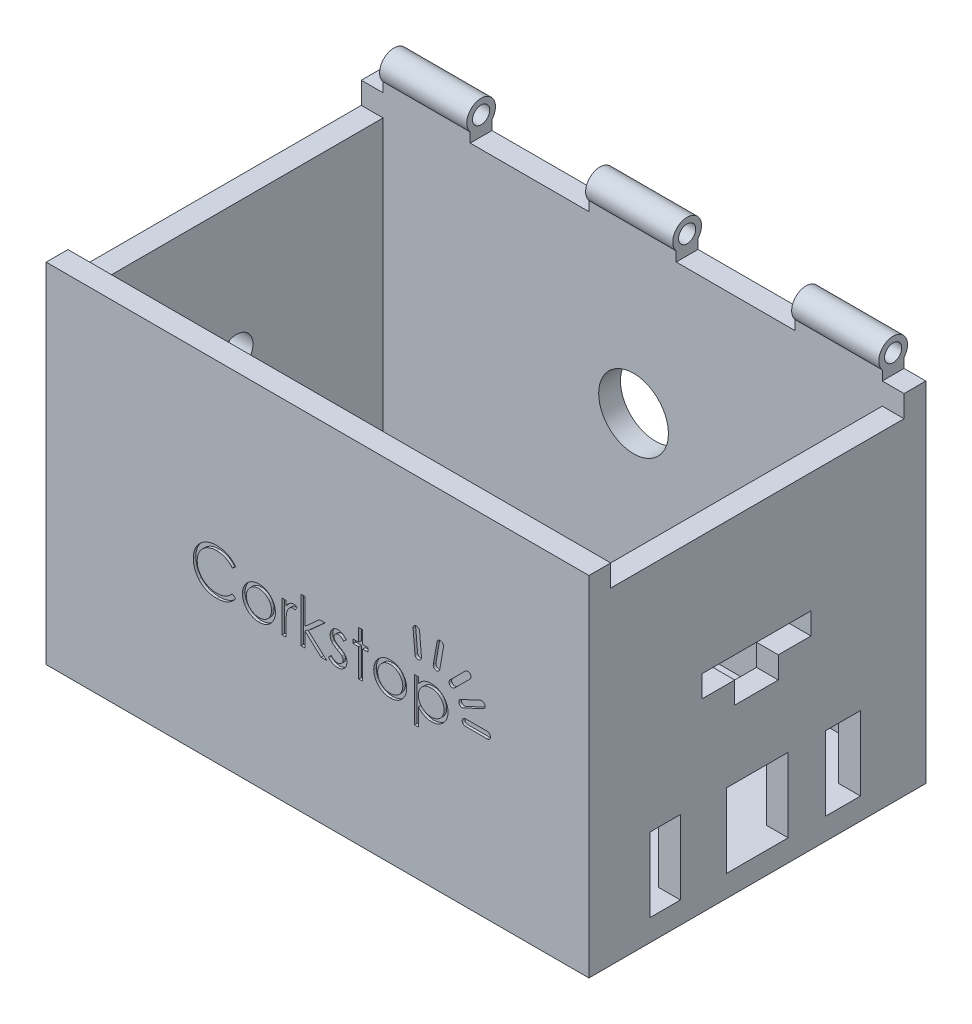
SolidWorks part; units mm, degrees
ref_plane "Front Plane" through (0, 0, 0) normal (0, 0, 1) x (1, 0, 0)
ref_plane "Top Plane" through (0, 0, 0) normal (0, 1, 0) x (1, 0, 0)
ref_plane "Right Plane" through (0, 0, 0) normal (1, 0, 0) x (0, 0, -1)
sketch "Sketch1" plane through (0, 0, 0) normal (0, 1, 0) x (1, 0, 0)
  line L1 (-79.1, 49.1) -> (79.1, 49.1)
  line L2 (-79.1, 49.1) -> (-79.1, -49.1)
  line L3 (-79.1, -49.1) -> (79.1, -49.1)
  line L4 (79.1, 49.1) -> (79.1, -49.1)
  line L5 (-79.1, 49.1) -> (79.1, -49.1) construction
  line L6 (-79.1, -49.1) -> (79.1, 49.1) construction
  point P0 (0, 0)
  dimension "D1" = 158.2
  dimension "D2" = 98.2
extrude "Boss-Extrude1" add sketch "Sketch1" along normal blind 6.35
sketch "Sketch2" plane through (0, 0, 49.1) normal (0, 0, 1) x (1, 0, 0)
  line L1 (-79.1, 101.6) -> (79.1, 101.6)
  line L2 (-79.1, 101.6) -> (-79.1, 6.35)
  line L3 (-79.1, 6.35) -> (79.1, 6.35)
  line L4 (79.1, 101.6) -> (79.1, 6.35)
  line L5 (-79.1, 101.6) -> (79.1, 6.35) construction
  line L6 (-79.1, 6.35) -> (79.1, 101.6) construction
  point P0 (0, 53.975)
  dimension "D1" = 95.25
extrude "Boss-Extrude2" add sketch "Sketch2" against normal blind 6.35
sketch "Sketch3" plane through (-79.1, 0, 0) normal (-1, 0, 0) x (0, 0, 1)
  line L1 (-42.75, 101.6) -> (42.75, 101.6)
  line L2 (-42.75, 101.6) -> (-42.75, 6.35)
  line L3 (-42.75, 6.35) -> (42.75, 6.35)
  line L4 (42.75, 101.6) -> (42.75, 6.35)
  line L5 (-42.75, 101.6) -> (42.75, 6.35) construction
  line L6 (-42.75, 6.35) -> (42.75, 101.6) construction
  point P0 (0, 53.975)
  dimension "D1" = 95.25
extrude "Boss-Extrude3" add sketch "Sketch3" against normal blind 6.35
sketch "Sketch4" plane through (0, 0, -49.1) normal (0, 0, -1) x (-1, 0, 0)
  line L1 (-79.1, 101.6) -> (79.1, 101.6)
  line L2 (-79.1, 101.6) -> (-79.1, 6.35)
  line L3 (-79.1, 6.35) -> (79.1, 6.35)
  line L4 (79.1, 101.6) -> (79.1, 6.35)
  line L5 (-79.1, 101.6) -> (79.1, 6.35) construction
  line L6 (-79.1, 6.35) -> (79.1, 101.6) construction
  point P0 (0, 53.975)
  dimension "D1" = 95.25
extrude "Boss-Extrude4" add sketch "Sketch4" against normal blind 6.35
sketch "Sketch5" plane through (79.1, 0, 0) normal (1, 0, 0) x (0, 0, -1)
  line L0 (42.75, 101.6) -> (42.75, 6.35) construction
  line L1 (-42.75, 27.94) -> (42.75, 27.94)
  line L2 (-42.75, 27.94) -> (-42.75, 101.6)
  line L3 (-42.75, 101.6) -> (42.75, 101.6)
  line L4 (42.75, 27.94) -> (42.75, 101.6)
  line L5 (-42.75, 27.94) -> (42.75, 101.6) construction
  line L6 (-42.75, 101.6) -> (42.75, 27.94) construction
  line L7 (42.75, 101.6) -> (42.75, 6.35) construction
  line L8 (42.75, 101.6) -> (49.1, 101.6) construction
  point P0 (0, 64.77)
  dimension "D1" = 73.66
  dimension "D2" = 0
extrude "Boss-Extrude5" add sketch "Sketch5" against normal blind 6.35
sketch "Sketch6" plane through (79.1, 0, 0) normal (1, 0, 0) x (0, 0, -1)
  line L0 (-42.75, 27.94) -> (42.75, 27.94) construction
  line L1 (-22.43, 27.94) -> (-8.968, 27.94)
  line L2 (-22.43, 27.94) -> (-22.43, 6.35)
  line L3 (-22.43, 6.35) -> (-8.968, 6.35)
  line L4 (-8.968, 27.94) -> (-8.968, 6.35)
  line L5 (-42.75, 6.35) -> (42.75, 6.35) construction
  line L6 (42.75, 6.35) -> (-42.75, 6.35) construction
  line L7 (8.968, 27.94) -> (19.89, 27.94)
  line L8 (8.968, 27.94) -> (8.968, 6.35)
  line L9 (8.968, 6.35) -> (19.89, 6.35)
  line L10 (19.89, 27.94) -> (19.89, 6.35)
  line L11 (-42.75, 6.35) -> (-42.75, 27.94) construction
  line L12 (42.75, 27.94) -> (42.75, 6.35) construction
  line L14 (-42.75, 27.94) -> (-31.32, 27.94)
  line L15 (-42.75, 27.94) -> (-42.75, 6.35)
  line L16 (-42.75, 6.35) -> (-31.32, 6.35)
  line L17 (-31.32, 27.94) -> (-31.32, 6.35)
  line L18 (42.75, 27.94) -> (30.05, 27.94)
  line L19 (42.75, 27.94) -> (42.75, 6.35)
  line L20 (42.75, 6.35) -> (30.05, 6.35)
  line L21 (30.05, 27.94) -> (30.05, 6.35)
  dimension "D1" = 13.462
  dimension "D2" = 10.922
  dimension "D3" = 20.32
  dimension "D4" = 22.86
  dimension "D5" = 0
  dimension "D6" = 11.43
  dimension "D7" = 12.7
  dimension "D8" = 17.936
extrude "Boss-Extrude6" add sketch "Sketch6" against normal blind 6.35
sketch "Çizim2" plane through (79.1, 0, 0) normal (1, 0, 0) x (0, 0, -1)
  line L0 (-49.1, 0) -> (49.1, 0) construction
  line L1 (-16.125, 60.325) -> (15.625, 60.325)
  line L2 (-16.125, 60.325) -> (-16.125, 53.975)
  line L3 (-16.125, 53.975) -> (-6.6, 53.975)
  line L4 (15.625, 60.325) -> (15.625, 53.975)
  line L5 (-16.125, 60.325) -> (15.625, 53.975) construction
  line L6 (-16.125, 53.975) -> (15.625, 60.325) construction
  line L7 (-42.75, 101.6) -> (-42.75, 6.35) construction
  line L8 (6.1, 53.975) -> (15.625, 53.975)
  line L9 (-6.6, 47.625) -> (6.1, 47.625)
  line L10 (-6.6, 47.625) -> (-6.6, 53.975)
  line L12 (6.1, 47.625) -> (6.1, 53.975)
  line L13 (-6.6, 47.625) -> (-0.25, 50.8) construction
  line L14 (-6.6, 53.975) -> (6.1, 47.625) construction
  point P0 (-0.25, 57.15)
  point P9 (-0.25, 50.8)
  dimension "D1" = 60.325
  dimension "D2" = 53.975
  dimension "D3" = 31.75
  dimension "D4" = 42.5
  dimension "D5" = 12.7
  dimension "D6" = 42.5
  dimension "D7" = 6.35
extrude "Kes-Ekstrüzyon1" cut sketch "Çizim2" against normal blind 6.35
sketch "Çizim3" plane through (0, 0, -49.1) normal (0, 0, -1) x (-1, 0, 0)
  line L0 (-79.1, 0) -> (79.1, 0) construction
  line L1 (-79.1, 101.6) -> (-79.1, 0) construction
  circle A0 centre (-0.25, 57.15) radius 10.16
  dimension "D1" = 20.32
  dimension "D2" = 57.15
  dimension "D3" = 78.85
extrude "Kes-Ekstrüzyon2" cut sketch "Çizim3" against normal blind 6.35
sketch "Çizim4" plane through (-79.1, 0, 0) normal (-1, 0, 0) x (0, 0, 1)
  line L0 (-49.1, 0) -> (49.1, 0) construction
  circle A0 centre (0, 57.15) radius 4.826
  dimension "D1" = 57.15
extrude "Kes-Ekstrüzyon3" cut sketch "Çizim4" against normal blind 6.35
sketch "Çizim5" plane through (79.1, 0, 0) normal (1, 0, 0) x (0, 0, -1)
  line L0 (42.75, 6.35) -> (42.75, 101.6) construction
  line L1 (-42.75, 101.6) -> (42.75, 101.6)
  line L2 (-42.75, 101.6) -> (-42.75, 95.25)
  line L3 (-42.75, 95.25) -> (42.75, 95.25)
  line L4 (42.75, 101.6) -> (42.75, 95.25)
  dimension "D1" = 6.35
extrude "Kes-Ekstrüzyon4" cut sketch "Çizim5" against normal blind 6.35
sketch "Çizim6" plane through (-79.1, 0, 0) normal (-1, 0, 0) x (0, 0, 1)
  line L1 (-42.75, 101.6) -> (42.75, 101.6)
  line L2 (-42.75, 101.6) -> (-42.75, 95.25)
  line L3 (-42.75, 95.25) -> (42.75, 95.25)
  line L4 (42.75, 101.6) -> (42.75, 95.25)
extrude "Kes-Ekstrüzyon5" cut sketch "Çizim6" against normal blind 6.35
sketch "Çizim7" plane through (0, 0, 49.1) normal (0, 0, 1) x (1, 0, 0)
  line L0 (-72.75, 6.35) -> (-72.75, 95.25) construction
  line L1 (-72.75, 6.35) -> (72.75, 6.35) construction
  text T0 "Corkstop" font "Century Gothic" height 12.7
  point P1 (0, 0)
  dimension "D1" = 35.56
  dimension "D2" = 35.56
extrude "Kes-Ekstrüzyon6" cut sketch "Çizim7" against normal blind 0.762
sketch "Çizim12" plane through (0, 0, 49.1) normal (0, 0, 1) x (1, 0, 0)
  line L2 (27.8371, 62.676) -> (28.3905, 56.3502)
  line L4 (29.7431, 62.8428) -> (30.2966, 56.517)
  arc A1 (28.3905, 56.3502) -> (30.2966, 56.517) centre (29.3435, 56.4336) ccw
  arc A2 (29.7431, 62.8428) -> (27.8371, 62.676) centre (28.7901, 62.7594) ccw
  dimension "D1" = 3.81
  dimension "D2" = 6.35
  dimension "D3" = 1.9133
  dimension "D4" = 6.35
  dimension "D5" = 6.35
extrude "Kes-Ekstrüzyon7" cut sketch "Çizim12" against normal blind 0.762
sketch "Çizim14" plane through (0, 0, 49.1) normal (0, 0, 1) x (1, 0, 0)
  line L1 (43.1131, 47.4484) -> (49.4631, 47.4484)
  line L3 (43.0101, 45.5351) -> (49.4631, 45.5351)
  arc A0 (49.4631, 45.5351) -> (49.4631, 47.4484) centre (49.4631, 46.4917) ccw
  arc A1 (43.1131, 47.4484) -> (43.0101, 45.5351) centre (43.1131, 46.489) ccw
  dimension "D1" = 1.9133
  dimension "D2" = 6.35
  dimension "D3" = 5.08
extrude "Kes-Ekstrüzyon8" cut sketch "Çizim14" against normal blind 0.762
sketch "Çizim15" plane through (0, 0, 49.1) normal (0, 0, 1) x (1, 0, 0)
  line L0 (41.7144, 51.6199) -> (47.4695, 54.3035)
  line L1 (42.4297, 49.8424) -> (48.2781, 52.5695)
  line L2 (49.4631, 47.4484) -> (43.1131, 47.4484) construction
  arc A0 (48.2781, 52.5695) -> (47.4695, 54.3035) centre (47.8738, 53.4365) ccw
  arc A1 (41.7144, 51.6199) -> (42.4297, 49.8424) centre (42.1199, 50.7504) ccw
  dimension "D1" = 1.9133
  dimension "D2" = 6.35
  dimension "D3" = 5.842
  dimension "D4" = 3.302
extrude "Kes-Ekstrüzyon9" cut sketch "Çizim15" against normal blind 0.762
sketch "Çizim18" plane through (0, 0, 49.1) normal (0, 0, 1) x (1, 0, 0)
  line L0 (38.6008, 54.9998) -> (43.0909, 59.4899)
  line L1 (39.8809, 53.5741) -> (44.4438, 58.137)
  arc A0 (44.4438, 58.137) -> (43.0909, 59.4899) centre (43.7674, 58.8135) ccw
  arc A1 (38.6008, 54.9998) -> (39.8809, 53.5741) centre (39.2792, 54.3214) ccw
  dimension "D1" = 1.9133
  dimension "D2" = 6.35
sketch "Çizim19" plane through (0, 0, 49.1) normal (0, 0, 1) x (1, 0, 0)
  line L0 (33.7349, 56.4717) -> (34.8376, 62.7252)
  line L1 (35.6013, 56.0381) -> (36.7218, 62.393)
  arc A0 (36.7218, 62.393) -> (34.8376, 62.7252) centre (35.7797, 62.5591) ccw
  arc A1 (33.7349, 56.4717) -> (35.6013, 56.0381) centre (34.6798, 56.3051) ccw
  dimension "D1" = 1.9133
  dimension "D2" = 6.35
extrude "Kes-Ekstrüzyon12" cut sketch "Çizim19" against normal blind 0.762
extrude "Kes-Ekstrüzyon13" cut sketch "Çizim18" against normal blind 0.762
sketch "Çizim21" plane through (-72.75, 0, 0) normal (1, 0, 0) x (0, 0, -1)
  line L1 (42.75, 101.6) -> (49.1, 101.6)
  line L2 (42.75, 101.6) -> (42.75, 104.3997)
  line L4 (49.1, 101.6) -> (49.1, 104.3997)
  arc A0 (49.1, 104.3997) -> (42.75, 104.3997) centre (45.925, 107.1365) ccw
  dimension "D1" = 6.35
  dimension "D2" = 3.175
extrude "Yükseklik-Ekstrüzyon2" add sketch "Çizim21" along normal blind 25.4
sketch "Çizim22" plane through (72.75, 0, 0) normal (-1, 0, 0) x (0, 0, 1)
  line L0 (-49.1, 101.6) -> (-42.75, 101.6)
  line L1 (-49.1, 101.6) -> (-49.1, 104.3995)
  line L2 (-42.75, 101.6) -> (-42.75, 104.3995)
  arc A0 (-42.75, 104.3995) -> (-49.1, 104.3995) centre (-45.925, 107.1364) ccw
  dimension "D1" = 6.35
  dimension "D2" = 3.175
extrude "Yükseklik-Ekstrüzyon3" add sketch "Çizim22" along normal blind 25.4
ref_plane "Düzlem2" through (12.7, 0, 0) normal (-1, 0, 0) x (0, 0, 1)
sketch "Çizim23" plane through (12.7, 0, 0) normal (-1, 0, 0) x (0, 0, 1)
  line L0 (-49.1, 101.6) -> (-42.75, 101.6)
  line L1 (-49.1, 101.6) -> (-49.1, 104.3997)
  line L2 (-42.75, 101.6) -> (-42.75, 104.3997)
  arc A0 (-42.75, 104.3997) -> (-49.1, 104.3997) centre (-45.925, 107.1365) ccw
  dimension "D1" = 6.35
  dimension "D2" = 3.175
extrude "Yükseklik-Ekstrüzyon4" add sketch "Çizim23" along normal blind 25.4
extrude "Yükseklik-Ekstrüzyon5" add sketch "Çizim23<2>" along normal blind 12.7
sketch "Çizim23<2>" plane through (12.7, 0, 0) normal (-1, 0, 0) x (0, 0, 1) same geometry as "Çizim23"
sketch "Çizim24" plane through (12.7, 0, 0) normal (-1, 0, 0) x (0, 0, 1)
  circle A0 centre (-45.925, 107.1365) radius 2.5
extrude "Kes-Ekstrüzyon14" cut sketch "Çizim24" along normal blind 25.4 contours A0
sketch "Çizim25" plane through (72.75, 0, 0) normal (1, 0, 0) x (0, 0, -1)
  circle A0 centre (45.925, 107.1364) radius 2.5
extrude "Kes-Ekstrüzyon15" cut sketch "Çizim25" against normal blind 25.4
sketch "Çizim26" plane through (-72.75, 0, 0) normal (-1, 0, 0) x (0, 0, 1)
  circle A0 centre (-45.925, 107.1365) radius 2.5
extrude "Kes-Ekstrüzyon16" cut sketch "Çizim26" against normal blind 25.4
